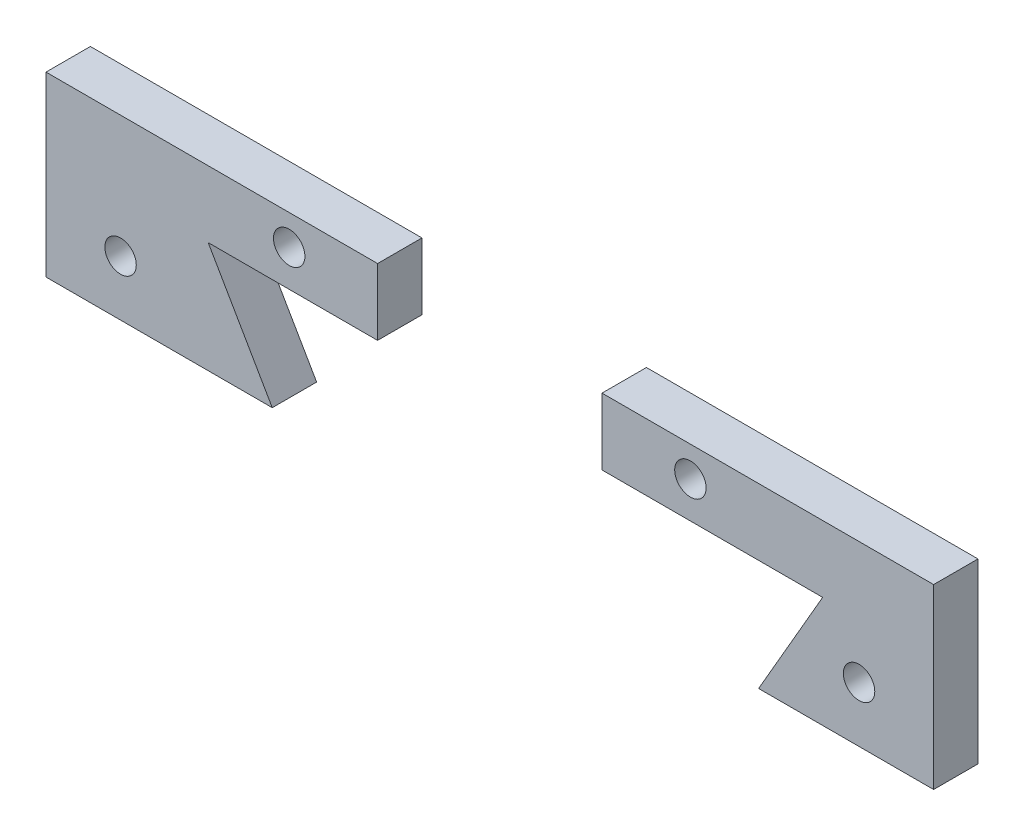
SolidWorks part; units mm, degrees
material "SAE F5 Wool Felt"
ref_plane "Front Plane" through (0, 0, 0) normal (0, 0, 1) x (1, 0, 0)
ref_plane "Top Plane" through (0, 0, 0) normal (0, 1, 0) x (1, 0, 0)
ref_plane "Right Plane" through (0, 0, 0) normal (1, 0, 0) x (0, 0, -1)
sketch "Sketch4" plane through (0, 0, 0) normal (0, 0, 1) x (1, 0, 0)
  point P0 (0, 0)
  line B0 (-63.5, -15.875) -> (63.5, -15.875)
  line B1 (63.5, 0) -> (38.4596, 0)
  line B2 (38.4596, 0) -> (47.625, 15.875)
  line B3 (47.625, 15.875) -> (16.0563, 15.875)
  line B4 (-40.2927, 15.875) -> (-31.1272, 0)
  line B5 (-31.1272, 0) -> (-63.5, 0)
  line B6 (-38.4596, 0) -> (-47.625, 15.875)
  line B7 (-47.625, 15.875) -> (-40.2927, 15.875)
  line B8 (-16.0563, 15.875) -> (-16.0563, -3.175)
  line B9 (-16.0563, 15.875) -> (-40.2927, 15.875)
  line B10 (-63.5, 0) -> (-63.5, 31.75)
  line B11 (-63.5, 31.75) -> (63.5, 31.75)
  line B12 (-16.0563, 15.875) -> (16.0563, 15.875)
  line B13 (0, 31.75) -> (0, -15.875) construction
  line B14 (-38.4596, 0) -> (38.4596, 0) construction
  line B15 (-28.702, 21.082) -> (28.702, 21.082) construction
  line B16 (-25.4, -8.001) -> (25.4, -8.001) construction
  line B17 (-52.832, 7.9375) -> (52.832, 7.9375) construction
  circle B18 centre (0, 6.35) radius 18.669 construction
sketch_block_instance "dovetail pair-1"
sketch_block "dovetail pair" parameters "D8"=37.338, "D1"=60, "D2"=127, "D3"=6.35, "D4"=15.875, "D5"=31.75, "D6"=95.25, "D7"=19.05, "D9"=60, "D10"=31.75, "D11"=50.8, "D12"=23.876, "D13"=7.874, "D14"=10.668, "D15"=34.798, "D16"=21.082, "D17"=7.9375
sketch "Sketch1" plane through (0, 0, 0) normal (0, 0, 1) x (1, 0, 0)
  line L0 (-31.1272, 0) -> (-63.5, 0) construction
  line L1 (-40.2927, 15.875) -> (-31.1272, 0) construction
  line L2 (38.4596, 0) -> (47.625, 15.875) construction
  line L3 (63.5, 0) -> (38.4596, 0) construction
  line L4 (-16.0563, 15.875) -> (-40.2927, 15.875) construction
  line L5 (47.625, 15.875) -> (16.0563, 15.875) construction
  line L6 (-31.1272, 0) -> (-63.5, 0)
  line L7 (-40.2927, 15.875) -> (-31.1272, 0)
  line L8 (38.4596, 0) -> (47.625, 15.875)
  line L9 (63.5, 0) -> (38.4596, 0)
  line L10 (-16.0563, 15.875) -> (-40.2927, 15.875)
  line L11 (47.625, 15.875) -> (16.0563, 15.875)
  line L12 (-63.5, 0) -> (-63.5, 25.4)
  line L13 (-63.5, 25.4) -> (-16.0563, 25.4)
  line L14 (-16.0563, 25.4) -> (-16.0563, 15.875)
  line L15 (16.0563, 15.875) -> (16.0563, 25.4)
  line L16 (16.0563, 25.4) -> (63.5, 25.4)
  line L17 (63.5, 25.4) -> (63.5, 0)
  dimension "D1" = 25.4
extrude "Boss-Extrude1" add sketch "Sketch1" along normal blind 6.35
hole_wizard "#8 Clearance Hole1" positions "Sketch2" profile "Sketch3" hole size "#8" standard "ANSI Inch" end condition through all
sketch "Sketch2" plane through (0, -15.875, 6.35) normal (0, 0, 1) x (1, 0, 0)
  point P32 (-52.832, 23.8125)
  point P34 (-28.702, 36.957)
  point P36 (28.702, 36.957)
  point P38 (52.832, 23.8125)
sketch "Sketch3" plane through (-52.832, 7.9375, 6.35) normal (1, 0, 0) x (0, -1, 0)
  line L0 (0, 0) -> (0, 6.35)
  line L1 (0, 6.35) -> (2.2479, 6.35)
  line L2 (2.2479, 6.35) -> (2.2479, 0)
  line L3 (2.2479, 0) -> (0, 0)
  line L4 (0, -6.35) -> (0, 107.95) construction
  dimension "Thru Hole Dia." = 4.4958
  dimension "Thru Hole Depth" = 6.35
equation "\"dovetail-angle\" = 60"
equation "\"dovetail-stock-width\" = 5"
equation "\"dovetail-stock-height\" = 1.25"
equation "\"dovetail-depth\" = 0.5 * \"dovetail-stock-height\""
equation "\"dovetail-throat-width\" = \"dovetail-stock-width\" - (2 * \"dovetail-depth\")"
equation "\"delta-x\" = 6"
equation "\"delta-y\" = 3"
equation "\"gib-thickness\" = 0.25"
equation "\"x-slide-length\" = \"dovetail-stock-width\" + \"delta-x\""
equation "\"y-slide-length\" = \"dovetail-stock-width\" + \"delta-y\""
equation "\"dog-point-diam\" = .149"
equation "\"dog-point-length\" = .067"
equation "\"dovetail-double-height\" = 2 * \"dovetail-depth\" + 0.5"
equation "\"acme-major-diam\" = .5"
equation "\"acme-pitch-diam\" = 0.45"
equation "\"acme-minor-diam\" = 0.4"
equation "\"acme-nut-od\" = 1.47"
equation "\"acme-nut-length\" = 1"
equation "\"acme-nut-trim-height\" = .75"
equation "\"screw-bearing-od\" = 0.5"
equation "\"screw-bearing-length\" = .375"
equation "\"screw-bearing-id\" = .375"
equation "\"end-plate-thickness\" = \"screw-bearing-length\""
equation "\"screw-add-length\" = 2 * \"end-plate-thickness\" + 1 + 0.5"
equation "\"x-screw-length\" = \"x-slide-length\" + \"screw-add-length\""
equation "\"y-screw-length\" = \"y-slide-length\" + \"screw-add-length\""
equation "\"acme-nut-mount-hole-space-horz\" = 0.95"
equation "\"acme-nut-mount-hole-space-vert\" = 0.5 * \"acme-nut-length\""
equation "\"vise-hole-center-dist\" = 6.75"
equation "\"wiper_plate_clearance\" = .03"
equation "\"D2@dovetail pair\"=\"dovetail-stock-width\""
equation "\"D1@dovetail pair\"=\"dovetail-angle\""
equation "\"D3@dovetail pair\"=\"gib-thickness\""
equation "\"D4@dovetail pair\"=\"dovetail-depth\""
equation "\"D5@dovetail pair\"=\"dovetail-stock-height\""
equation "\"D6@dovetail pair\"=\"dovetail-throat-width\""
equation "\"D10@dovetail pair\"=\"dovetail-stock-height\""
equation "\"D7@dovetail pair\"=\"acme-nut-trim-height\""
equation "\"D8@dovetail pair\"=\"acme-nut-od\""
equation "\"D9@dovetail pair\"=\"dovetail-angle\""
equation "\"D17@dovetail pair\"=\"dovetail-depth\"/2"
